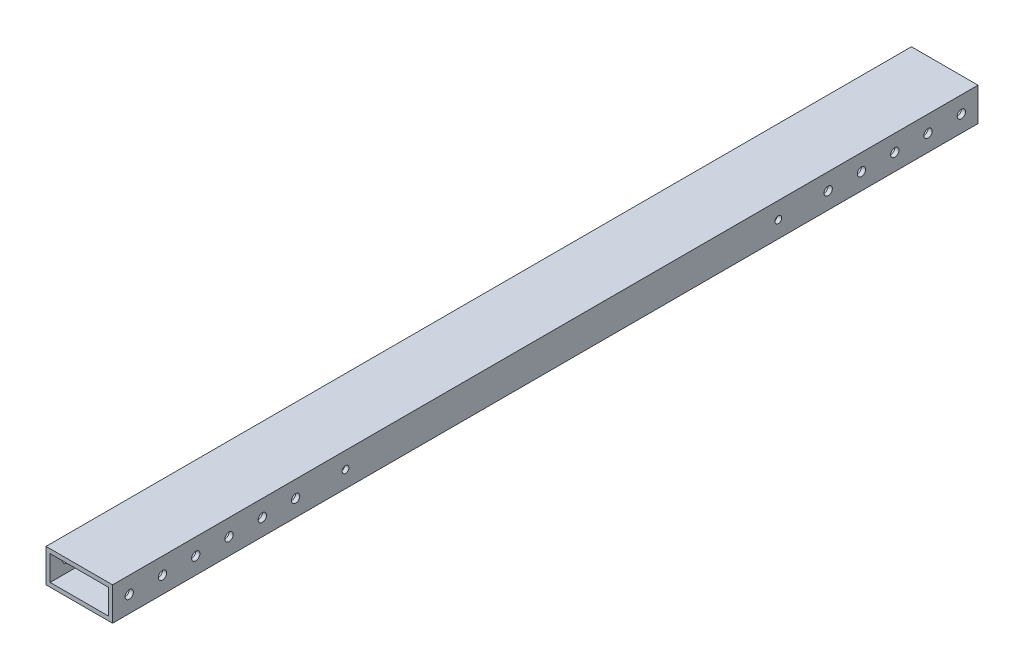
SolidWorks part; units mm, degrees
material "6061 Alloy"
ref_plane "Front Plane" through (0, 0, 0) normal (0, 0, 1) x (1, 0, 0)
ref_plane "Top Plane" through (0, 0, 0) normal (0, 1, 0) x (1, 0, 0)
ref_plane "Right Plane" through (0, 0, 0) normal (1, 0, 0) x (0, 0, -1)
sketch "Sketch1" plane through (0, 0, 0) normal (0, 0, 1) x (1, 0, 0)
  line L0 (-22.225, 9.525) -> (22.225, 9.525)
  line L2 (-25.4, 12.7) -> (25.4, 12.7)
  line L3 (-25.4, 12.7) -> (-25.4, -12.7)
  line L4 (-25.4, -12.7) -> (25.4, -12.7)
  line L5 (25.4, 12.7) -> (25.4, -12.7)
  line L10 (22.225, 9.525) -> (22.225, -9.525)
  line L11 (-22.225, -9.525) -> (22.225, -9.525)
  line L12 (-22.225, 9.525) -> (-22.225, -9.525)
  point P12 (0, 12.7)
  point P14 (25.4, 0)
  dimension "Wall Thickness" = 3.175
  dimension "Outside Width" = 50.8
  dimension "Outside Height" = 25.4
  dimension "Inside Height" = 19.05
  dimension "Inside Width" = 44.45
sketch "Sketch2" plane through (0, 0, 0) normal (1, 0, 0) x (0, 0, -1)
  line L0 (330.2, 0) -> (-330.2, 0)
  point P4 (0, 0)
  point P7 (-330.2, 0)
  point P10 (330.2, 0)
  dimension "Length" = 660.4
sketch "Sketch3" plane through (0, 0, 0) normal (0, 0, 1) x (1, 0, 0)
  line L21 (25.4, 12.7) -> (-25.4, 12.7)
  line L22 (25.4, -12.7) -> (25.4, 12.7)
  line L23 (-25.4, -12.7) -> (25.4, -12.7)
  line L24 (-25.4, 12.7) -> (-25.4, -12.7)
  line L25 (25.4, 12.7) -> (-25.4, 12.7)
  line L26 (25.4, -12.7) -> (25.4, 12.7)
  line L27 (-25.4, -12.7) -> (25.4, -12.7)
  line L28 (-25.4, 12.7) -> (-25.4, -12.7)
  line L29 (22.225, 9.525) -> (-22.225, 9.525)
  line L30 (22.225, -9.525) -> (22.225, 9.525)
  line L31 (-22.225, -9.525) -> (22.225, -9.525)
  line L32 (-22.225, 9.525) -> (-22.225, -9.525)
  line L33 (22.225, 9.525) -> (-22.225, 9.525)
  line L34 (22.225, -9.525) -> (22.225, 9.525)
  line L35 (-22.225, -9.525) -> (22.225, -9.525)
  line L36 (-22.225, 9.525) -> (-22.225, -9.525)
  dimension "D1" = 0
  dimension "D2" = 0
extrude "Boss-Extrude1" add sketch "Sketch3" along normal up to vertex (330.2 mm away) and the other way up to vertex (330.2 mm away) up to point (0, 0, 330.2) other way up to point (0, 0, -330.2)
sketch "Drawing Reference" plane through (0, 0, 0) normal (1, 0, 0) x (0, 0, -1)
  line L0 (-330.2, 0) -> (330.2, 0) construction
  line L1 (0, -12.7) -> (0, 12.7) construction
  line L2 (-330.2, -12.7) -> (330.2, -12.7) construction
  line L5 (-330.2, 12.7) -> (330.2, 12.7) construction
  point P7 (-293.624, 0)
  point P8 (293.624, 0)
  dimension "D1" = 36.576
sketch "Sketch5" plane through (25.4, 0, 0) normal (1, 0, 0) x (0, 0, -1)
  line L2 (-266.7, 0) -> (-241.3, 0)
  line L3 (-241.3, 0) -> (-215.9, 0)
  line L4 (-215.9, 0) -> (-190.5, 0)
  line L5 (-317.5, 0) -> (-330.2, 0)
  line L6 (-330.2, -12.7) -> (-330.2, 12.7) construction
  line L7 (-317.5, 0) -> (-292.1, 0)
  line L8 (-292.1, 0) -> (-266.7, 0)
sketch "Sketch8" plane through (25.4, 0, 0) normal (1, 0, 0) x (0, 0, -1)
  line L0 (330.2, 0) -> (292.1, 0)
  line L1 (330.2, -12.7) -> (330.2, 12.7) construction
  line L2 (292.1, 0) -> (266.7, 0)
  line L3 (266.7, 0) -> (241.3, 0)
  line L4 (241.3, 0) -> (215.9, 0)
  line L5 (330.2, 0) -> (317.5, 0)
hole_wizard "1/4 (0.25) Diameter Hole3" positions "Sketch12" profile "Sketch13" hole size "1/4" standard "ANSI Inch" end condition through all
sketch "Sketch12" plane through (-25.4, 0, 0) normal (-1, 0, 0) x (0, 0, 1)
  point P4 (-317.5, 0)
sketch "Sketch13" plane through (-25.4, 0, -317.5) normal (0, 1, 0) x (0, 0, 1)
  line L0 (0, 0) -> (0, 50.8)
  line L1 (0, 50.8) -> (3.175, 50.8)
  line L2 (3.175, 50.8) -> (3.175, 0)
  line L5 (3.175, 0) -> (0, 0)
  line L11 (0, -6.35) -> (0, 107.95) construction
  dimension "Thru Hole Dia." = 6.35
  dimension "Thru Hole Depth" = 50.8
hole_wizard "1/4 (0.25) Diameter Hole4" positions "Sketch14" profile "Sketch15" hole size "1/4" standard "ANSI Inch" end condition through all
sketch "Sketch14" plane through (-25.4, 0, 0) normal (-1, 0, 0) x (0, 0, 1)
  point P0 (292.1, 0)
  point P3 (317.5, 0)
  point P6 (0, 0)
  point P7 (292.1, 0)
  point P9 (330.2, 0)
  point P10 (317.5, 0)
sketch "Sketch15" plane through (-25.4, 0, 292.1) normal (0, 1, 0) x (0, 0, 1)
  line L0 (0, 0) -> (0, 50.8)
  line L1 (0, 50.8) -> (3.175, 50.8)
  line L2 (3.175, 50.8) -> (3.175, 0)
  line L5 (3.175, 0) -> (0, 0)
  line L11 (0, -6.35) -> (0, 107.95) construction
  dimension "Thru Hole Dia." = 6.35
  dimension "Thru Hole Depth" = 50.8
hole_wizard "1/4 (0.25) Diameter Hole5" positions "Sketch17" profile "Sketch18" hole size "1/4" standard "ANSI Inch" end condition through all
sketch "Sketch17" plane through (25.4, 0, 0) normal (1, 0, 0) x (0, 0, -1)
  point P0 (292.1, 0)
  point P3 (266.7, 0)
sketch "Sketch18" plane through (25.4, 0, -292.1) normal (0, 1, 0) x (0, 0, -1)
  line L0 (0, 0) -> (0, 50.8)
  line L1 (0, 50.8) -> (3.175, 50.8)
  line L2 (3.175, 50.8) -> (3.175, 0)
  line L5 (3.175, 0) -> (0, 0)
  line L11 (0, -6.35) -> (0, 107.95) construction
  dimension "Thru Hole Dia." = 6.35
  dimension "Thru Hole Depth" = 50.8
hole_wizard "1/4 (0.25) Diameter Hole6" positions "Sketch19" profile "Sketch20" hole size "1/4" standard "ANSI Inch" end condition through all
sketch "Sketch19" plane through (25.4, 0, 0) normal (1, 0, 0) x (0, 0, -1)
  point P0 (215.9, 0)
  point P3 (241.3, 0)
sketch "Sketch20" plane through (25.4, 0, -215.9) normal (0, 1, 0) x (0, 0, -1)
  line L0 (0, 0) -> (0, 50.8)
  line L1 (0, 50.8) -> (3.175, 50.8)
  line L2 (3.175, 50.8) -> (3.175, 0)
  line L5 (3.175, 0) -> (0, 0)
  line L11 (0, -6.35) -> (0, 107.95) construction
  dimension "Thru Hole Dia." = 6.35
  dimension "Thru Hole Depth" = 50.8
hole_wizard "1/4 (0.25) Diameter Hole7" positions "Sketch21" profile "Sketch22" hole size "1/4" standard "ANSI Inch" end condition through all
sketch "Sketch21" plane through (25.4, 0, 0) normal (1, 0, 0) x (0, 0, -1)
  point P0 (-190.5, 0)
  point P3 (-215.9, 0)
sketch "Sketch22" plane through (25.4, 0, 190.5) normal (0, 1, 0) x (0, 0, -1)
  line L0 (0, 0) -> (0, 50.8)
  line L1 (0, 50.8) -> (3.175, 50.8)
  line L2 (3.175, 50.8) -> (3.175, 0)
  line L5 (3.175, 0) -> (0, 0)
  line L11 (0, -6.35) -> (0, 107.95) construction
  dimension "Thru Hole Dia." = 6.35
  dimension "Thru Hole Depth" = 50.8
hole_wizard "1/4 (0.25) Diameter Hole8" positions "Sketch23" profile "Sketch24" hole size "1/4" standard "ANSI Inch" end condition through all
sketch "Sketch23" plane through (25.4, 0, 0) normal (1, 0, 0) x (0, 0, -1)
  point P0 (-266.7, 0)
  point P3 (-241.3, 0)
sketch "Sketch24" plane through (25.4, 0, 266.7) normal (0, 1, 0) x (0, 0, -1)
  line L0 (0, 0) -> (0, 50.8)
  line L1 (0, 50.8) -> (3.175, 50.8)
  line L2 (3.175, 50.8) -> (3.175, 0)
  line L5 (3.175, 0) -> (0, 0)
  line L11 (0, -6.35) -> (0, 107.95) construction
  dimension "Thru Hole Dia." = 6.35
  dimension "Thru Hole Depth" = 50.8
sketch "Sketch25" plane through (25.4, 0, 0) normal (1, 0, 0) x (0, 0, -1)
  line L0 (-190.5, 0) -> (-152.4, 0)
  line L1 (215.9, 0) -> (177.8, 0)
hole_wizard "13/64 (0.20313) Diameter Hole1" positions "Sketch26" profile "Sketch27" hole size "13/64" standard "ANSI Inch" end condition through all
sketch "Sketch26" plane through (25.4, 0, 0) normal (1, 0, 0) x (0, 0, -1)
  point P0 (-152.4, 0)
  point P3 (177.8, 0)
sketch "Sketch27" plane through (25.4, 0, 152.4) normal (0, 1, 0) x (0, 0, -1)
  line L0 (0, 0) -> (0, 50.8)
  line L1 (0, 50.8) -> (2.5798, 50.8)
  line L2 (2.5798, 50.8) -> (2.5798, 0)
  line L5 (2.5798, 0) -> (0, 0)
  line L11 (0, -6.35) -> (0, 107.95) construction
  dimension "Thru Hole Dia." = 5.1595
  dimension "Thru Hole Depth" = 50.8
sketch "Sketch30" plane through (-25.4, 0, 0) normal (-1, 0, 0) x (0, 0, 1)
  point P0 (-128.5875, 0)
  point P1 (-103.1875, 0)
  point P2 (77.7875, 0)
  point P3 (103.1875, 0)
hole_wizard "1/2 (0.5) Diameter Hole1" positions "Sketch33" profile "Sketch34" hole size "1/2" standard "ANSI Inch"
sketch "Sketch33" plane through (-25.4, 0, 0) normal (-1, 0, 0) x (0, 0, 1)
  point P0 (-128.5875, 0)
  point P3 (-103.1875, 0)
  point P7 (77.7875, 0)
  point P10 (103.1875, 0)
sketch "Sketch34" plane through (-25.4, 0, -128.5875) normal (0, 1, 0) x (0, 0, 1)
  line L0 (0, 0) -> (0, 10.1655)
  line L1 (0, 10.1655) -> (6.35, 6.35)
  line L2 (6.35, 6.35) -> (6.35, 0)
  line L5 (6.35, 0) -> (0, 0)
  line L10 (0, 10.1655) -> (-6.35, 6.35) construction
  line L11 (0, -6.35) -> (0, 107.95) construction
  dimension "Hole Dia." = 12.7
  dimension "Hole Depth" = 6.35
  dimension "Drill Angle" = 118
equation "\"D1@Drawing Reference\"=\"Outside Width@Sketch1\" * 0.72"
